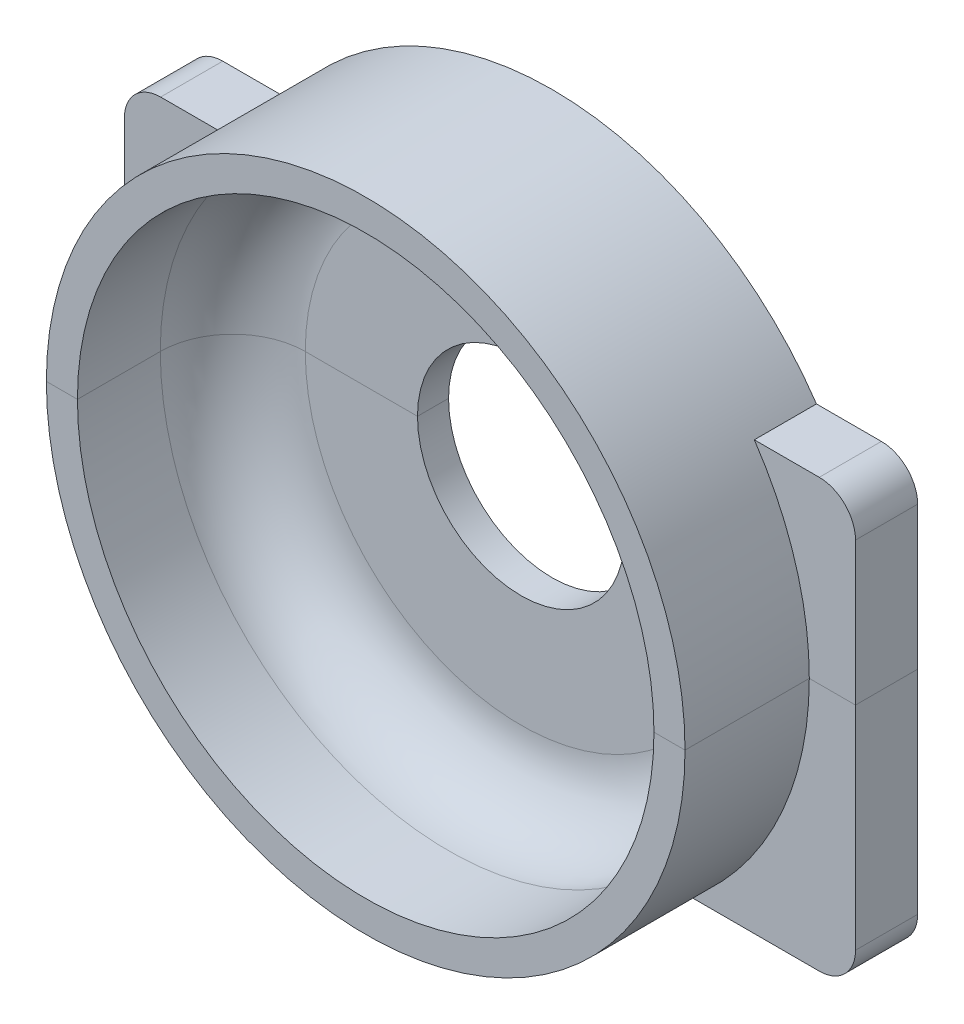
SolidWorks part; units mm, degrees
ref_plane "Front Plane" through (0, 0, 0) normal (0, 0, 1) x (1, 0, 0)
ref_plane "Top Plane" through (0, 0, 0) normal (0, 1, 0) x (1, 0, 0)
ref_plane "Right Plane" through (0, 0, 0) normal (1, 0, 0) x (0, 0, -1)
sketch "Sketch2" plane through (0, 0, 0) normal (0, 0, 1) x (1, 0, 0)
  line L0 (-63.558, 3.3692) -> (-63.558, -6.6308) construction
  line L1 (-63.558, -0.1308) -> (7.042, -0.1308)
  line L2 (-63.558, -0.1308) -> (-63.558, 41.1692)
  line L3 (-63.558, 41.1692) -> (7.042, 41.1692)
  line L4 (7.042, -0.1308) -> (7.042, 41.1692)
  line L5 (7.042, 47.6692) -> (7.042, 37.6692) construction
  line L6 (-53.558, -0.1308) -> (-60.058, -0.1308) construction
  line L7 (-60.058, 41.1692) -> (-53.558, 41.1692) construction
  circle A0 centre (-28.2554, 23.8718) radius 10
  circle A1 centre (-28.2554, 23.8718) radius 30.836
  arc A4 (-63.558, 3.3692) -> (-60.058, -0.1308) centre (-60.058, 3.3692) ccw
  arc A5 (-63.558, 3.3692) -> (-60.058, -0.1308) centre (-60.058, 3.3692) ccw
  arc A13 (-60.058, 41.1692) -> (-63.558, 37.6692) centre (-60.058, 37.6692) ccw
  arc A14 (-60.058, 41.1692) -> (-63.558, 37.6692) centre (-60.058, 37.6692) ccw
  arc A16 (7.042, 37.6692) -> (3.542, 41.1692) centre (3.542, 37.6692) ccw
  arc A17 (7.042, 37.6692) -> (3.542, 41.1692) centre (3.542, 37.6692) ccw
  arc A19 (3.542, -0.1308) -> (7.042, 3.3692) centre (3.542, 3.3692) ccw
  arc A20 (3.542, -0.1308) -> (7.042, 3.3692) centre (3.542, 3.3692) ccw
  circle M7 centre (-58.558, 4.8692) radius 2.3812
  line M8 (-63.558, 9.8692) -> (-63.558, 3.3692)
  arc M9 (-63.558, 3.3692) -> (-60.058, -0.1308) centre (-60.058, 3.3692) ccw
  line M10 (-60.058, -0.1308) -> (-53.558, -0.1308)
  line M11 (-53.558, -0.1308) -> (-53.558, 9.8692)
  line M12 (-53.558, 9.8692) -> (-63.558, 9.8692)
  dimension "D7" = 20
  dimension "D1" = 0
  dimension "D2" = 0
  dimension "D3" = 0
  dimension "D4" = 0
  dimension "D5" = 0
  dimension "D6" = 0
extrude "Boss-Extrude1" add sketch "Sketch2" along normal blind 3 contours A1 L3 L2 M12 | L3 A1 | L3 A1 L1 A0 M12 M11 | L1 A1 | A1 L1 M11 | A1 L1 L4 L3 | A1 M12 M11 | A1 M12 M8 M9 M10 M11 M7 | M7 region at (-62.4329, 0.9943, 0) region at (-51.671, 1.8923, 0) region at (-60.4161, 26.1238, 0) region at (-50.2693, 3.353, 0) region at (-28.2554, -2.8919, 0) region at (-54.3006, 8.6313, 0) region at (2.819, 17.9068, 0) region at (-28.2554, 46.7015, 0) region at (-58.558, 4.8692, 0)
sketch "Sketch3" plane through (0, 0, 3) normal (0, 0, 1) x (1, 0, 0)
  circle A0 centre (-28.2554, 23.8718) radius 30.836
  circle A1 centre (-28.2554, 23.8718) radius 27.836
  arc A2 (-47.6133, -0.1308) -> (-8.8974, -0.1308) centre (-28.2554, 23.8718) ccw construction
  dimension "D1" = 3
  dimension "D2" = 0
extrude "Boss-Extrude2" add sketch "Sketch3" along normal blind 15
fillet "Fillet1" radius 7 1 edges at (-0.4194, 23.8718, 3)
sketch "Sketch4" plane through (0, 0, 3) normal (0, 0, 1) x (1, 0, 0)
  circle A0 centre (-28.2554, 23.8718) radius 10
  circle A1 centre (-28.2554, 23.8718) radius 11
  circle A2 centre (-28.2554, 23.8718) radius 10 construction
  dimension "D1" = 1
  dimension "D2" = 0
extrude "Boss-Extrude3" [suppressed] add sketch "Sketch4" along normal blind 2
fillet "Fillet2" [suppressed] radius 2
sketch "Sketch7" plane through (0, 0, 3) normal (0, 0, 1) x (1, 0, 0)
  line L6 (-8.8974, -0.1308) -> (3.542, -0.1308)
  line L7 (7.042, 3.3692) -> (7.042, 37.6692)
  line L8 (3.542, 41.1692) -> (-2.7277, 41.1692)
  line L9 (-8.8974, -0.1308) -> (3.542, -0.1308)
  line L10 (7.042, 3.3692) -> (7.042, 37.6692)
  line L11 (3.542, 41.1692) -> (-2.7277, 41.1692)
  line L15 (-53.783, 41.1692) -> (-60.058, 41.1692)
  line L16 (-63.558, 37.6692) -> (-63.558, 3.3692)
  line L17 (-60.058, -0.1308) -> (-47.6133, -0.1308)
  line L18 (-53.783, 41.1692) -> (-60.058, 41.1692)
  line L19 (-63.558, 37.6692) -> (-63.558, 3.3692)
  line L20 (-60.058, -0.1308) -> (-47.6133, -0.1308)
  arc A6 (-8.8974, -0.1308) -> (-2.7277, 41.1692) centre (-28.2554, 23.8718) ccw
  arc A7 (3.542, -0.1308) -> (7.042, 3.3692) centre (3.542, 3.3692) ccw
  arc A8 (7.042, 37.6692) -> (3.542, 41.1692) centre (3.542, 37.6692) ccw
  arc A9 (-8.8974, -0.1308) -> (-2.7277, 41.1692) centre (-28.2554, 23.8718) ccw
  arc A10 (3.542, -0.1308) -> (7.042, 3.3692) centre (3.542, 3.3692) ccw
  arc A11 (7.042, 37.6692) -> (3.542, 41.1692) centre (3.542, 37.6692) ccw
  arc A15 (-53.783, 41.1692) -> (-47.6133, -0.1308) centre (-28.2554, 23.8718) ccw
  arc A16 (-60.058, 41.1692) -> (-63.558, 37.6692) centre (-60.058, 37.6692) ccw
  arc A17 (-63.558, 3.3692) -> (-60.058, -0.1308) centre (-60.058, 3.3692) ccw
  arc A18 (-53.783, 41.1692) -> (-47.6133, -0.1308) centre (-28.2554, 23.8718) ccw
  arc A19 (-60.058, 41.1692) -> (-63.558, 37.6692) centre (-60.058, 37.6692) ccw
  arc A20 (-63.558, 3.3692) -> (-60.058, -0.1308) centre (-60.058, 3.3692) ccw
  dimension "D1" = 0
  dimension "D2" = 0
extrude "Boss-Extrude4" add sketch "Sketch7" along normal blind 3
sketch "Sketch6" plane through (0, 0, 0) normal (0, 0, -1) x (-1, 0, 0)
  circle A0 centre (58.558, 4.8692) radius 2.3812
  circle A1 centre (58.558, 33.8692) radius 2.3812
  circle A2 centre (-2.042, 33.8692) radius 2.3812
  circle A3 centre (-2.042, 4.8692) radius 2.3813
extrude "Cut-Extrude1" cut sketch "Sketch6" against normal blind 3.175
ref_point "Point1"
ref_plane "Plane2" through (0, 23.8718, 0) normal (0, 1, 0) x (1, 0, 0)
split "Split1" trim tools "Plane2" bodies to split 108 resulting bodies 110 111
